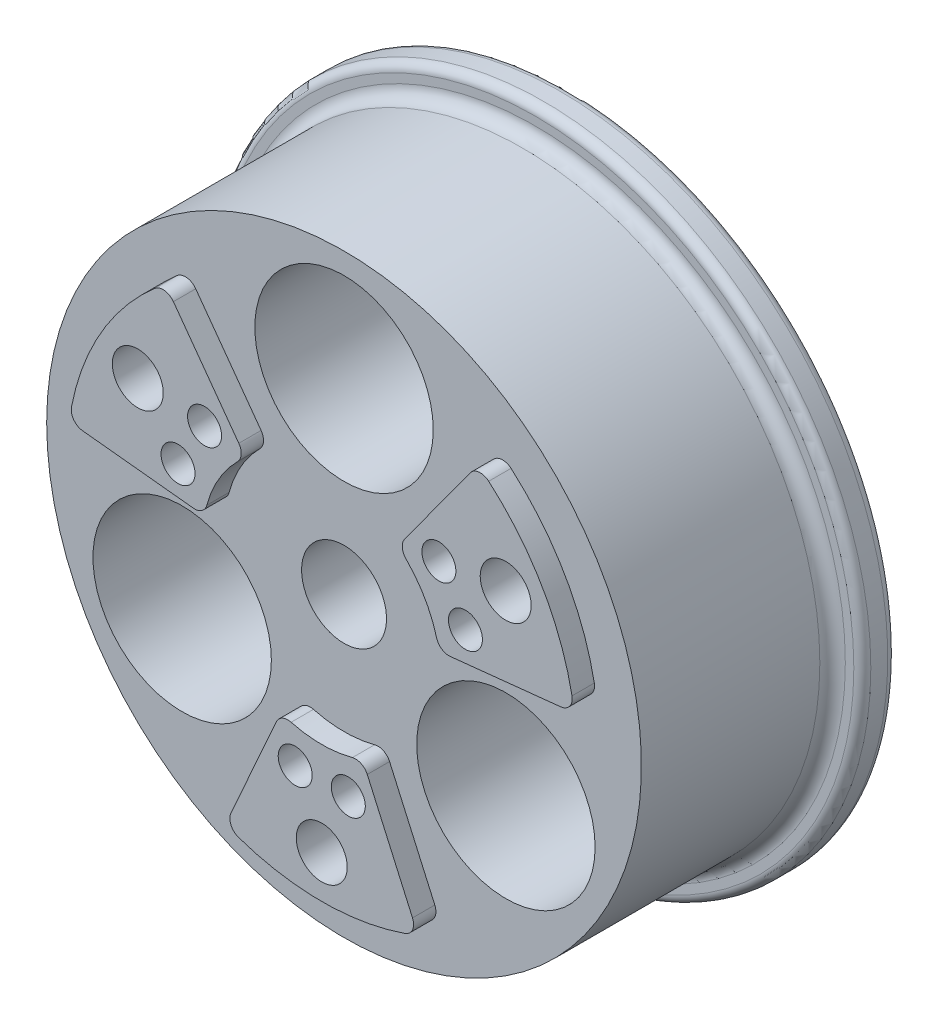
SolidWorks part; units mm, degrees
ref_plane "Plan de face" through (0, 0, 0) normal (0, 0, 1) x (1, 0, 0)
ref_plane "Plan de dessus" through (0, 0, 0) normal (0, 1, 0) x (1, 0, 0)
ref_plane "Plan de droite" through (0, 0, 0) normal (1, 0, 0) x (0, 0, -1)
sketch "Esquisse1" plane through (0, 0, 0) normal (1, 0, 0) x (0, 0, -1)
  line L0 (0, 10) -> (0, 77)
  line L1 (0, 77) -> (-8, 77)
  line L2 (-8, 77) -> (-8, 70)
  line L3 (-8, 70) -> (-53, 70)
  line L4 (-53, 70) -> (-53, 10)
  line L5 (-53, 10) -> (0, 10)
  line L6 (0, 0) -> (-128.5484, 0) construction
  dimension "D1" = 10
  dimension "D2" = 77
  dimension "D3" = 70
  dimension "D4" = 8
  dimension "D5" = 53
revolve "Révolution1" add sketch "Esquisse1" angle 360 about L6
sketch "Esquisse2" plane through (0, 0, 53) normal (0, 0, 1) x (1, 0, 0)
  line L0 (0, 0) -> (0, 66.8222) construction
  line L1 (0, 0) -> (0, 44) construction
  line L2 (0, 0) -> (67.185, 0) construction
  line L3 (0, 0) -> (76.2102, 44) construction
  line L4 (17.9544, 21.4858) -> (36.7837, 47.4021)
  line L5 (27.5844, 4.8061) -> (59.4433, 8.1546)
  line L6 (9.63, -26.2919) -> (22.6595, -55.5567)
  line L7 (-9.63, -26.2919) -> (-22.6595, -55.5567)
  line L8 (-27.5844, 4.8061) -> (-59.4433, 8.1546)
  line L9 (-17.9544, 21.4858) -> (-36.7837, 47.4021)
  circle A0 centre (0, 44) radius 21
  arc A6 (27.5844, 4.8061) -> (17.9544, 21.4858) centre (0, 0) ccw
  circle A8 centre (38.1051, -22) radius 21
  circle A9 centre (-38.1051, -22) radius 21
  arc A11 (-22.6595, -55.5567) -> (22.6595, -55.5567) centre (0, 0) ccw
  arc A12 (59.4433, 8.1546) -> (36.7837, 47.4021) centre (0, 0) ccw
  arc A13 (-9.63, -26.2919) -> (9.63, -26.2919) centre (0, 0) ccw
  arc A14 (-36.7837, 47.4021) -> (-59.4433, 8.1546) centre (0, 0) ccw
  arc A15 (-17.9544, 21.4858) -> (-27.5844, 4.8061) centre (0, 0) ccw
  dimension "D2" = 42
  dimension "D9" = 3
  dimension "D6" = 60
  dimension "D4" = 44
  dimension "D5" = 30
  dimension "D7" = 24
  dimension "D8" = 24
  dimension "D3" = 3
extrude "Enlèv. mat.-Extru.1" cut sketch "Esquisse2" against normal through all both and the other way through all contours A0 | A9 | A8 region at (0, 44, 53) region at (38.1051, -22, 53) region at (-38.1051, -22, 53)
extrude "Boss.-Extru.1" add sketch "Esquisse2<3>" along normal blind 5.25 contours L5 A12 L4 A6 | A15 L9 A14 L8 | A13 L7 A11 L6 region at (39.0329, 22.5357, 53) region at (0, -45.0713, 53) region at (-39.0329, 22.5357, 53)
sketch "Esquisse2<3>" plane through (0, 0, 53) normal (0, 0, 1) x (1, 0, 0) same geometry as "Esquisse2"
sketch "Esquisse3" plane through (0, 0, 0) normal (0, 0, -1) x (-1, 0, 0)
  line L0 (0, 0) -> (-76.2102, 44) construction
  line L1 (0, 0) -> (-27.5776, 23.1404) construction
  line L2 (0, 0) -> (-33.8289, 12.3127) construction
  line L3 (-17.9544, 21.4858) -> (-36.7837, 47.4021) construction
  line L4 (-27.5844, 4.8061) -> (-59.4433, 8.1546) construction
  line L5 (-43.3013, 25) -> (0, 0) construction
  line L6 (43.3013, 25) -> (0, 0) construction
  line L7 (0, -50) -> (0, 0) construction
  line L8 (0, 0) -> (-27.5776, 23.1404) construction
  circle A0 centre (-43.3013, 25) radius 6
  circle A1 centre (-27.5776, 23.1404) radius 4
  circle A2 centre (-33.8289, 12.3127) radius 4
  circle A3 centre (0, 0) radius 36 construction
  circle A4 centre (0, 0) radius 50 construction
  circle A5 centre (33.8289, 12.3127) radius 4
  circle A6 centre (27.5776, 23.1404) radius 4
  circle A7 centre (43.3013, 25) radius 6
  circle A8 centre (-6.2513, -35.4531) radius 4
  circle A9 centre (6.2513, -35.4531) radius 4
  circle A10 centre (0, -50) radius 6
  dimension "D1" = 8
  dimension "D2" = 8
  dimension "D3" = 12
  dimension "D4" = 72
  dimension "D5" = 100
  dimension "D6" = 14
  dimension "D7" = 14
  dimension "D8" = 3
hole_wizard "Trous de centrage Ø8.0mm1" positions "Esquisse3D1" profile "Esquisse4" hole size "Ø8.0" standard "ISO" end condition through all
sketch3d "Esquisse3D1"
  point P0 (27.5776, 23.1404, 0)
  point P3 (33.8289, 12.3127, 0)
  point P6 (6.2513, -35.4531, 0)
  point P9 (-6.2513, -35.4531, 0)
  point P12 (-33.8289, 12.3127, 0)
  point P15 (-27.5776, 23.1404, 0)
sketch "Esquisse4" plane through (27.5776, 23.1404, 0) normal (1, 0, 0) x (0, 1, 0)
  line L0 (0, 0) -> (0, 58.25)
  line L1 (0, 58.25) -> (4, 58.25)
  line L2 (4, 58.25) -> (4, 0)
  line L5 (4, 0) -> (0, 0)
  line L11 (0, -6.35) -> (0, 107.95) construction
  dimension "Diamètre du perçage jusqu'au prochain" = 8
  dimension "Profondeur du perçage jusqu'au prochain" = 58.25
hole_wizard "Perçage3" positions "Esquisse3D6" profile "Esquisse8" legacy end condition through all
sketch3d "Esquisse3D6"
  point P0 (43.3013, 25, 0)
  point P3 (-43.3013, 25, 0)
  point P6 (0, -50, 0)
sketch "Esquisse8" plane through (43.3013, 25, 0) normal (1, 0, 0) x (0, 1, 0)
  line L0 (0, 0) -> (0, 58.25)
  line L1 (0, 58.25) -> (6, 58.25)
  line L2 (6, 58.25) -> (6, 46.25)
  line L3 (6, 46.25) -> (9, 46.25)
  line L4 (9, 46.25) -> (9, 0)
  line L5 (9, 0) -> (0, 0)
  line L6 (0, 110) -> (0, -10) construction
  dimension "Diamètre" = 12
  dimension "Profondeur" = 58.25
  dimension "Diamètre chambrage" = 18
  dimension "Profondeur chambrage" = 46.25
fillet "Congé1" radius 3 1 edges at (-70, 0, 8)
fillet "Congé2" radius 2 2 edges at (-77, 0, 8) (-77, 0, 0)
fillet "Congé3" radius 1 13 edges at (2.2513, -35.4531, 0) (-52.3013, 25, 0) (-31.5776, 23.1404, 0) (34.3013, 25, 0) (23.5776, 23.1404, 0) (29.8289, 12.3127, 0) (59.1051, -22, 0) (-10, 0, 0) (-10.2513, -35.4531, 0) (-9, -50, 0) (-17.1051, -22, 0) (-37.8289, 12.3127, 0) (21, 44, 0)
fillet "Congé6" radius 3 12 edges at (-9.63, -26.2919, 55.625) (-22.6595, -55.5567, 55.625) (22.6595, -55.5567, 55.625) (9.63, -26.2919, 55.625) (-36.7837, 47.4021, 55.625) (-59.4433, 8.1546, 55.625) (-17.9544, 21.4858, 55.625) (-27.5844, 4.8061, 55.625) (27.5844, 4.8061, 55.625) (17.9544, 21.4858, 55.625) (36.7837, 47.4021, 55.625) (59.4433, 8.1546, 55.625)
